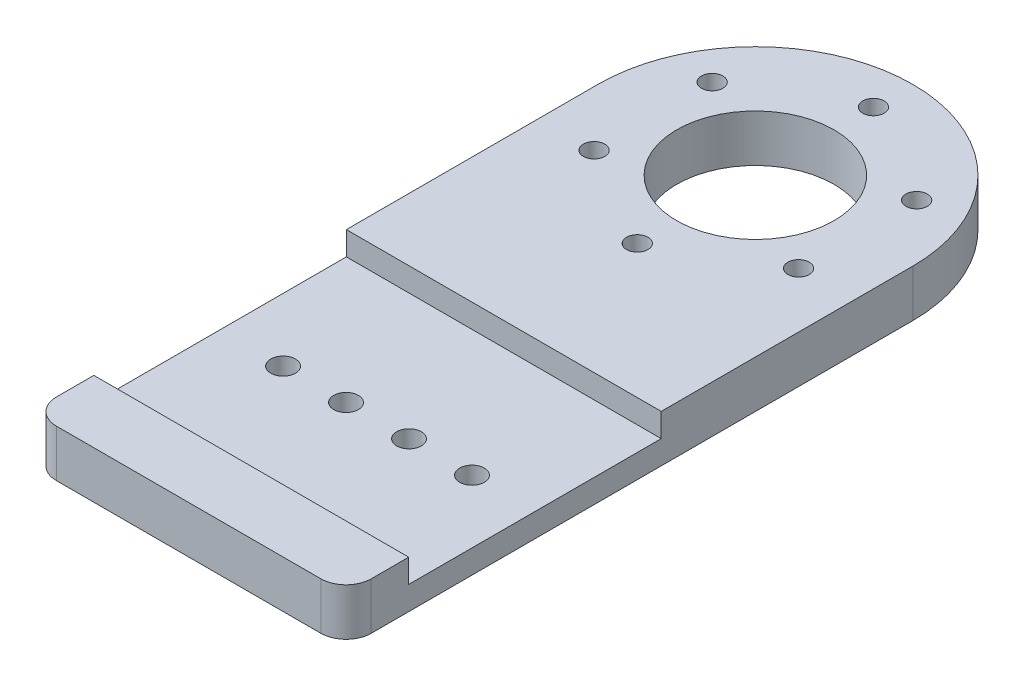
SolidWorks part; units mm, degrees
ref_plane "Front Plane" through (0, 0, 0) normal (0, 0, 1) x (1, 0, 0)
ref_plane "Top Plane" through (0, 0, 0) normal (0, 1, 0) x (1, 0, 0)
ref_plane "Right Plane" through (0, 0, 0) normal (1, 0, 0) x (0, 0, -1)
sketch "Sketch1" plane through (0, 0, 0) normal (0, 1, 0) x (1, 0, 0)
  line L0 (0, 12.6365) -> (63.5, 12.6365)
  line L2 (0, 114.3) -> (0, 0)
  line L3 (0, 0) -> (63.5, 0)
  line L4 (63.5, 114.3) -> (63.5, 0)
  line L5 (31.75, 114.3) -> (31.75, 146.05) construction
  line L7 (0, 63.5635) -> (63.5, 63.5635)
  circle A0 centre (31.75, 114.3) radius 15.875
  circle A1 centre (12.7, 38.1) radius 2.4892
  circle A2 centre (25.4, 38.1) radius 2.4892
  circle A3 centre (38.1, 38.1) radius 2.4892
  circle A4 centre (50.8, 38.1) radius 2.4892
  arc A8 (63.5, 114.3) -> (0, 114.3) centre (31.75, 114.3) ccw
  point P0 (0, 0)
  point P25 (63.5, -9.7091)
  dimension "D3" = 31.75
  dimension "D4" = 114.3
  dimension "D5" = 31.75
  dimension "D6" = 4.9784
  dimension "D7" = 12.7
  dimension "D8" = 25.4635
  dimension "D2" = 31.75
  dimension "D11" = 12.7
  dimension "D10" = 12.6365
  dimension "D12" = 63.5635
  dimension "D9" = 4
extrude "Boss-Extrude2" add sketch "Sketch1" along normal blind 9.525 contours L4 L0 L2 L3 | L2 L7 L4 A0 | A0 region at (31.75, 0, -6.3182) region at (1.041, 0, -88.9317)
extrude "Boss-Extrude3" add sketch "Sketch1<3>" along normal blind 4.7625 contours L7 L2 L0 L4 A4 A3 A2 A1 region at (31.75, 0, -38.1)
sketch "Sketch1<3>" plane through (0, 0, 0) normal (0, 1, 0) x (1, 0, 0) same geometry as "Sketch1"
sketch "Sketch2" plane through (0, 0, 0) normal (0, -1, 0) x (1, 0, 0)
  line L0 (31.75, -114.3) -> (11.1278, -102.3938) construction
  line L1 (31.75, -114.3) -> (31.75, -90.4875) construction
  circle A0 centre (11.1278, -102.3938) radius 2.159
  circle A4 centre (31.75, -114.3) radius 23.8125 construction
  circle A5 centre (31.75, -90.4875) radius 2.159
  circle A6 centre (52.3722, -102.3938) radius 2.159
  circle A7 centre (52.3722, -126.2063) radius 2.159
  circle A8 centre (31.75, -138.1125) radius 2.159
  circle A9 centre (11.1278, -126.2062) radius 2.159
  dimension "D1" = 4.318
  dimension "D3" = 60
  dimension "D4" = 47.625
  dimension "D2" = 6
extrude "Cut-Extrude1" cut sketch "Sketch2" against normal through all
sketch "Sketch3" plane through (0, 0, 0) normal (0, -1, 0) x (1, 0, 0)
  line L0 (-939.958, 0) -> (49060.042, 0) construction
  line L2 (63.5, -875.9909) -> (63.5, 49124.0091) construction
  point P3 (63.5, 0)
fillet "Fillet1" radius 5.08 2 edges at (0, 4.7625, 0) (63.5, 4.7625, 0)
